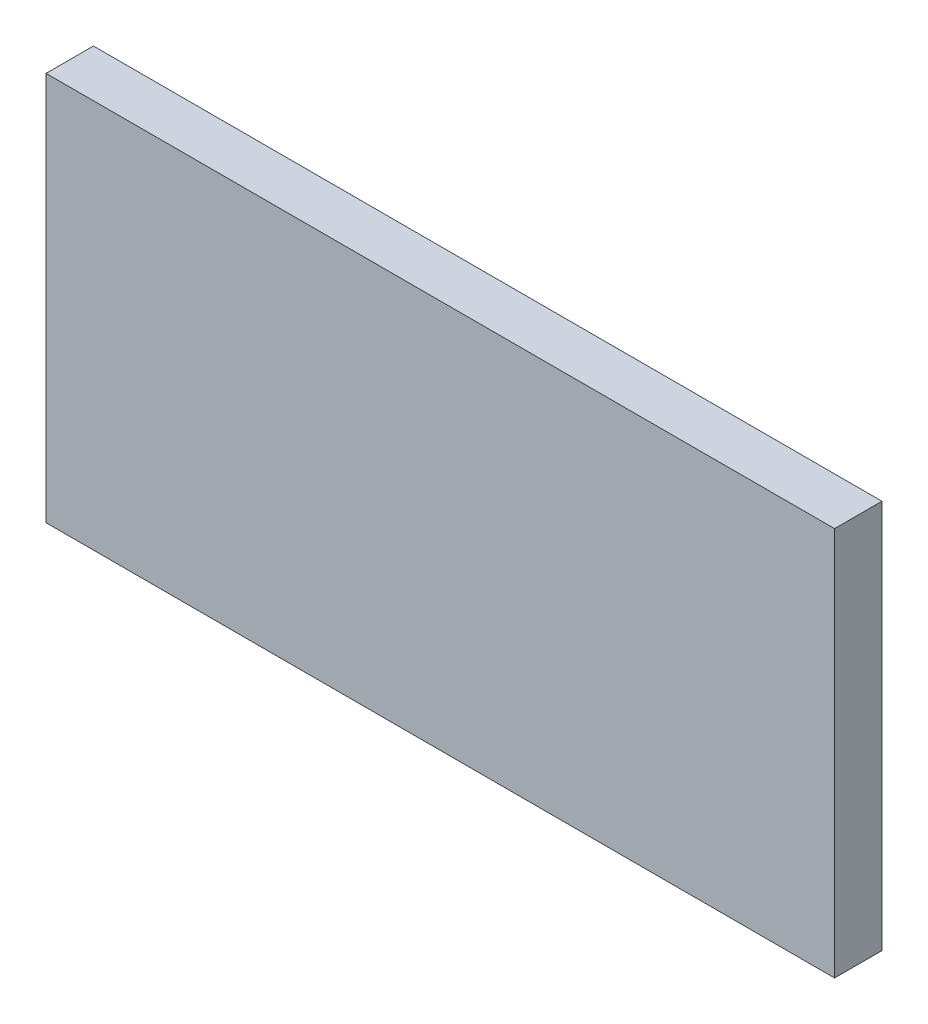
SolidWorks part; units mm, degrees
ref_plane "Front Plane" through (0, 0, 0) normal (0, 0, 1) x (1, 0, 0)
ref_plane "Top Plane" through (0, 0, 0) normal (0, 1, 0) x (1, 0, 0)
ref_plane "Right Plane" through (0, 0, 0) normal (1, 0, 0) x (0, 0, -1)
sketch "Sketch1" plane through (0, 0, 0) normal (0, 0, 1) x (1, 0, 0)
  line L0 (156.6828, 77.7073) -> (-151.7229, -74.4997) construction
  line L1 (156.6828, -74.4997) -> (-151.7229, -74.4997)
  line L2 (156.6828, -74.4997) -> (156.6828, 77.7073)
  line L3 (156.6828, 77.7073) -> (-151.7229, 77.7073)
  line L4 (-151.7229, -74.4997) -> (-151.7229, 77.7073)
  line L5 (-151.7229, 77.7073) -> (156.6828, -74.4997) construction
  arc A0 (156.0147, 3.7084) -> (155.8597, 7.2972) centre (154.1428, 5.4253) ccw construction
  arc A1 (-150.944, -61.2022) -> (-138.8373, -73.8872) centre (-142.1979, -64.9747) ccw construction
  circle A3 centre (120.1011, 42.6789) radius 35.0284 construction
  point P0 (0, 0)
extrude "Boss-Extrude1" add sketch "Sketch1" against normal blind 18.542
